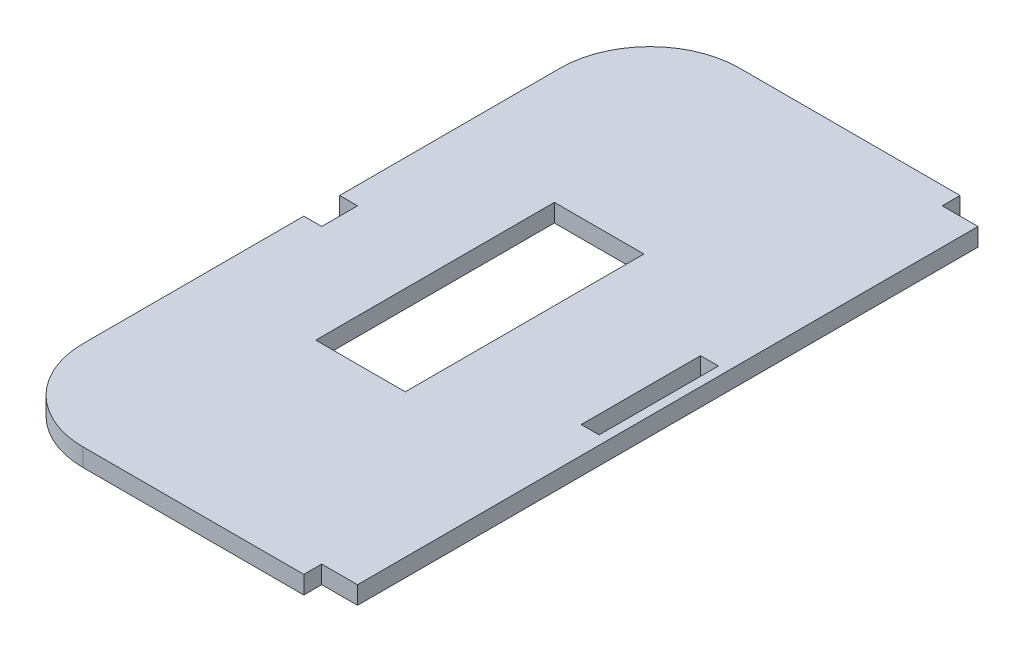
SolidWorks part; units mm, degrees
ref_plane "Спереди" through (0, 0, 0) normal (0, 0, 1) x (1, 0, 0)
ref_plane "Сверху" through (0, 0, 0) normal (0, 1, 0) x (1, 0, 0)
ref_plane "Справа" through (0, 0, 0) normal (1, 0, 0) x (0, 0, -1)
other "Configuration Table"
sketch "Эскиз4" plane through (0, 0, 0) normal (0, 1, 0) x (1, 0, 0)
  line L0 (0, 58) -> (0, 110)
  line L1 (0, 0) -> (52, 0)
  line L2 (0, 0) -> (0, 52)
  line L3 (0, 110) -> (52, 110)
  line L6 (55, 107) -> (52, 107)
  line L7 (52, 107) -> (55, 107)
  line L8 (55, 107) -> (58, 107)
  line L9 (52, 107) -> (52, 110)
  line L10 (58, 107) -> (58, 110)
  line L12 (55, 3) -> (58, 3)
  line L13 (55, 3) -> (52, 3)
  line L14 (52, 3) -> (52, 0)
  line L15 (3, 55) -> (3, 58)
  line L16 (3, 55) -> (3, 52)
  line L17 (3, 58) -> (0, 58)
  line L18 (3, 52) -> (0, 52)
  line L25 (55, 107) -> (55, 3) construction
  line L26 (3, 55) -> (73, 55)
  line L28 (58, 107) -> (58, 3)
  dimension "D1" = 3
  dimension "D2" = 3
  dimension "D3" = 3
  dimension "D5" = 3
  dimension "D6" = 3
  dimension "D7" = 3
extrude "Бобышка-Вытянуть3" add sketch "Эскиз4" along normal blind 3 contours L3 L10 L8 L6 L9 L2 L17 L15 L16 L18 L1 L14 L13 L12 | L25 L6 L9 L3 L0 L17 L15 L26 | L8 L25 L26 L10 | L26 L25 L12 region at (27.5, 0, -82.5) region at (27.5, 0, -27.5) region at (56.5, 0, -29) region at (56.5, 0, -81)
sketch "Sketch1" plane through (0, 3, 0) normal (0, 1, 0) x (1, 0, 0)
  line L0 (3, 52) -> (3, 58) construction
  line L13 (3, 55) -> (107, 55) construction
  line L15 (55, 107) -> (55, 3) construction
  line L16 (52, 107) -> (58, 107) construction
  line L17 (58, 3) -> (52, 3) construction
  line L19 (19, 75) -> (34, 75)
  line L20 (19, 75) -> (19, 35)
  line L21 (19, 35) -> (34, 35)
  line L22 (34, 75) -> (34, 35)
  line L23 (53.5, 65) -> (56.5, 65)
  line L24 (53.5, 65) -> (53.5, 45)
  line L25 (53.5, 45) -> (56.5, 45)
  line L26 (56.5, 65) -> (56.5, 45)
  dimension "D1" = 3
  dimension "D2" = 20
  dimension "D3" = 16
  dimension "D4" = 15
  dimension "D5" = 40
extrude "Cut-Extrude1" cut sketch "Sketch1" against normal blind 10
fillet "Fillet1" radius 15 2 edges at (0, 1.5, 0) (0, 1.5, -110)
